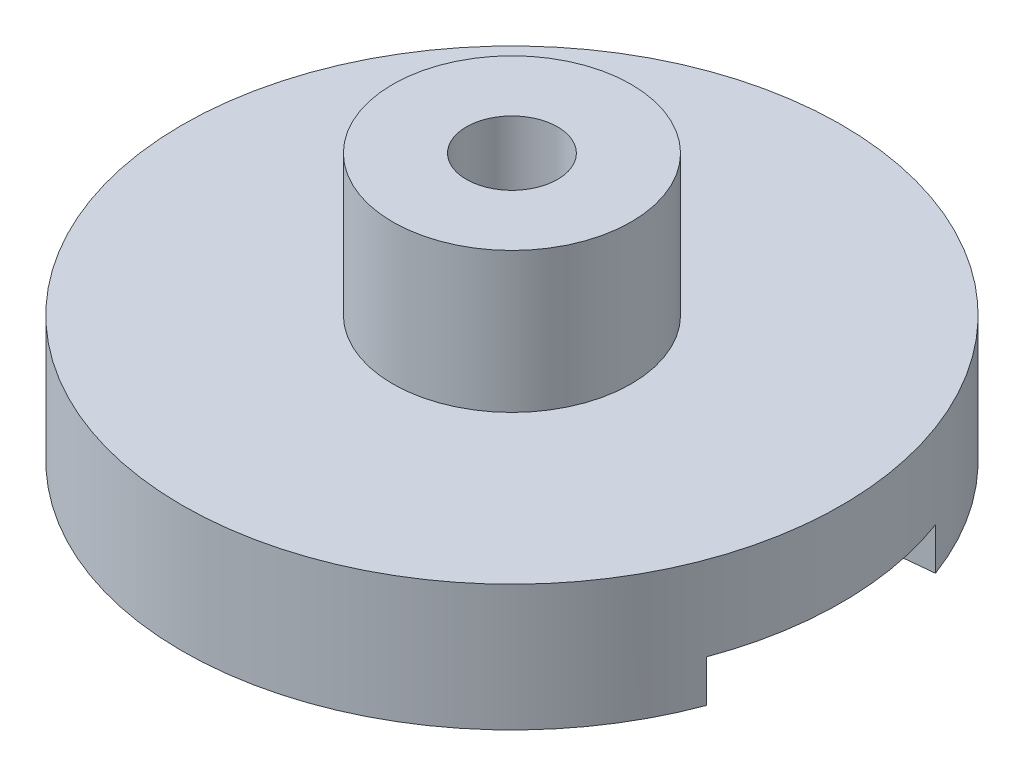
SolidWorks part; units mm, degrees
ref_plane "Спереди" through (0, 0, 0) normal (0, 0, 1) x (1, 0, 0)
ref_plane "Сверху" through (0, 0, 0) normal (0, 1, 0) x (1, 0, 0)
ref_plane "Справа" through (0, 0, 0) normal (1, 0, 0) x (0, 0, -1)
sketch "Эскиз1" plane through (0, 0, 0) normal (0, 1, 0) x (1, 0, 0)
  line L0 (-15.5, 2.19) -> (15.5, -5.29) construction
  line L1 (15.5, -5.29) -> (15.5, 5.29) construction
  line L2 (15.5, 5.29) -> (-15.5, -2.19) construction
  line L3 (-15.5, -2.19) -> (-15.5, 2.19) construction
  line L8 (-15.699, -4.1801) -> (22.1104, -7.961)
  line L10 (22.1104, 7.961) -> (-15.699, 4.1801)
  line L11 (-17.5, 2.19) -> (-17.5, -2.19)
  line L12 (-15.5, 2.19) -> (15.5, 5.29) construction
  line L13 (-15.5, -2.19) -> (15.5, -5.29) construction
  line L14 (-17.5, 0) -> (15.5, 0) construction
  line L15 (22.0905, 8.1601) -> (-15.7189, 4.3791)
  line L16 (-17.7, 2.19) -> (-17.7, -2.19)
  line L17 (-15.7189, -4.3791) -> (22.0905, -8.1601)
  circle A6 centre (0, 0) radius 23.5
  arc A9 (-15.699, 4.1801) -> (-17.5, 2.19) centre (-15.5, 2.19) ccw
  arc A10 (-17.5, -2.19) -> (-15.699, -4.1801) centre (-15.5, -2.19) ccw
  arc A11 (-15.7189, 4.3791) -> (-17.7, 2.19) centre (-15.5, 2.19) ccw
  arc A12 (-17.7, -2.19) -> (-15.7189, -4.3791) centre (-15.5, -2.19) ccw
  point P4 (15.5, 0)
  point P5 (0, 0)
  point P6 (0, 0)
  point P8 (0, 0)
  point P16 (0, 0)
  point P19 (0, 0)
  point P21 (22.1098, -7.9627)
  point P22 (22.1104, 7.961)
  dimension "D3" = 47
  dimension "D4" = 0.2
extrude "Бобышка-Вытянуть1" add sketch "Эскиз1" along normal blind 3 contours A6
extrude "Вырез-Вытянуть1" cut sketch "Эскиз1<4>" along normal blind 3 contours L16 A12 L17 A6 L8 A10 L11 A9 L10 L15 A11 | L11 A10 L8 A6 L10 A9 region at (5.1051, 0, 0) region at (3.2014, 0, 6.1134)
sketch "Эскиз1<4>" plane through (0, 0, 0) normal (0, 1, 0) x (1, 0, 0) same geometry as "Эскиз1"
sketch "Эскиз2" plane through (0, 3, 0) normal (0, 1, 0) x (1, 0, 0)
  circle A1 centre (0, 0) radius 23.5
extrude "Бобышка-Вытянуть2" add sketch "Эскиз2" along normal blind 6
sketch "Эскиз3" plane through (0, 9, 0) normal (0, 1, 0) x (1, 0, 0)
  circle A0 centre (0, 0) radius 8.5
  dimension "D1" = 17
extrude "Бобышка-Вытянуть3" add sketch "Эскиз3" along normal blind 10
sketch "Эскиз4" plane through (0, 19, 0) normal (0, 1, 0) x (1, 0, 0)
  circle A0 centre (0, 0) radius 3.25
  dimension "D1" = 6.5
extrude "Вырез-Вытянуть2" cut sketch "Эскиз4" against normal blind 19
sketch "Эскиз5" plane through (0, 3, 0) normal (0, -1, 0) x (1, 0, 0)
  line L1 (5.7735, 0) -> (2.8868, 5)
  line L2 (2.8868, 5) -> (-2.8868, 5)
  line L3 (-2.8868, 5) -> (-5.7735, 0)
  line L4 (-5.7735, 0) -> (-2.8868, -5)
  line L5 (-2.8868, -5) -> (2.8868, -5)
  line L6 (2.8868, -5) -> (5.7735, 0)
  circle A0 centre (0, 0) radius 5 construction
  dimension "D1" = 10
extrude "Вырез-Вытянуть3" cut sketch "Эскиз5" against normal blind 4.5
